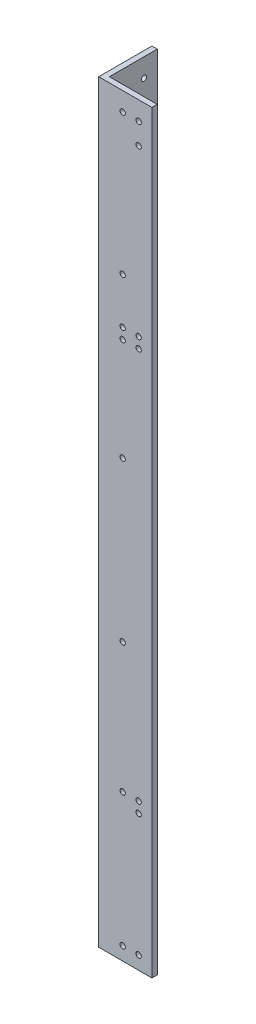
SolidWorks part; units mm, degrees
ref_plane "Front Plane" through (0, 0, 0) normal (0, 0, 1) x (1, 0, 0)
ref_plane "Top Plane" through (0, 0, 0) normal (0, 1, 0) x (1, 0, 0)
ref_plane "Right Plane" through (0, 0, 0) normal (1, 0, 0) x (0, 0, -1)
sketch "Sketch2" plane through (0, 0, 0) normal (0, 1, 0) x (1, 0, 0)
  line L0 (0, 31.75) -> (3.175, 31.75)
  line L1 (3.175, 31.75) -> (3.175, 3.175)
  line L2 (3.175, 3.175) -> (31.75, 3.175)
  line L3 (31.75, 3.175) -> (31.75, 0)
  line L4 (31.75, 0) -> (0, 0)
  line L5 (0, 0) -> (0, 31.75)
  point P9 (1.5875, 31.75)
  point P10 (31.75, 1.5875)
  dimension "D4" = 3.175
  dimension "D1" = 31.75
  dimension "D2" = 31.75
  dimension "D3" = 3.175
extrude "Boss-Extrude1" add sketch "Sketch2" along normal blind 450
sketch "BackSideHoles-Sketch3" plane through (0, 0, 0) normal (0, 0, 1) x (1, 0, 0)
  line L0 (0, 0) -> (31.75, 0) construction
  line L1 (0, 450) -> (0, 0) construction
  circle A1 centre (23.8125, 81.1125) radius 1.5875
  circle A2 centre (14.2875, 87.4625) radius 1.5875
  circle A3 centre (23.8125, 87.4625) radius 1.5875
  circle A4 centre (14.2875, 438.8875) radius 1.5875
  circle A6 centre (23.8125, 438.8875) radius 1.5875
  circle A7 centre (23.8125, 426.1875) radius 1.5875
  circle A10 centre (14.2875, 327.6026) radius 1.5875
  circle A11 centre (23.8125, 327.6026) radius 1.5875
  circle A12 centre (14.2875, 321.2526) radius 1.5875
  circle A13 centre (23.8125, 321.2526) radius 1.5875
  circle A14 centre (14.2875, 165) radius 1.5875
  circle A15 centre (14.2875, 260) radius 1.5875
  circle A16 centre (14.2875, 355) radius 1.5875
  circle A17 centre (14.2875, 7.9375) radius 1.5875
  circle A18 centre (23.8125, 7.9375) radius 1.5875
  dimension "D4" = 3.175
  dimension "D8" = 11.1125
  dimension "D7" = 6.35
  dimension "D10" = 327.6026
  dimension "D11" = 165
  dimension "D12" = 95
  dimension "D13" = 95
  dimension "D6" = 7.9375
  dimension "D5" = 6.35
  dimension "D14" = 81.1125
  dimension "D3" = 9.525
  dimension "D2" = 14.2875
  dimension "D9" = 12.7
sketch "RightSideHoles-Sketch4" plane through (0, 0, 0) normal (-1, 0, 0) x (0, 0, 1)
  line L0 (-31.75, 450) -> (0, 450) construction
  line L1 (0, 450) -> (0, 0) construction
  line L3 (-31.75, 0) -> (0, 0) construction
  circle A0 centre (-23.8125, 81.1125) radius 1.5875
  circle A2 centre (-23.8125, 87.4625) radius 1.5875
  circle A4 centre (-23.8125, 438.8875) radius 1.5875
  circle A5 centre (-14.2875, 426.1875) radius 1.5875
  circle A6 centre (-23.8125, 426.1875) radius 1.5875
  circle A10 centre (-23.8125, 327.6026) radius 1.5875
  circle A11 centre (-14.2875, 327.6026) radius 1.5875
  circle A12 centre (-23.8125, 314.9026) radius 1.5875
  circle A13 centre (-14.2875, 314.9026) radius 1.5875
  circle A14 centre (-23.8125, 7.9375) radius 1.5875
  circle A15 centre (-14.2875, 7.9375) radius 1.5875
  circle A16 centre (-14.2875, 165) radius 1.5875
  circle A17 centre (-14.2875, 260) radius 1.5875
  circle A18 centre (-14.2875, 355) radius 1.5875
  circle A19 centre (-14.2875, 81.1125) radius 1.5875
  dimension "D4" = 3.175
  dimension "D10" = 327.6026
  dimension "D13" = 95
  dimension "D5" = 6.35
  dimension "D2" = 14.2875
  dimension "D9" = 12.7
  dimension "D6" = 11.1125
  dimension "D8" = 7.9375
  dimension "D7" = 12.7
  dimension "D12" = 165
  dimension "D14" = 95
  dimension "D3" = 81.1125
  dimension "D11" = 9.525
extrude "BackSideHoles-Cut-Extrude1" cut sketch "BackSideHoles-Sketch3" against normal blind 3.175
extrude "RightSideHoles-Cut-Extrude2" cut sketch "RightSideHoles-Sketch4" against normal blind 3.175
equation "\"RailThickness\"= .125in'Spec"
equation "\"VSWidth\"= 1.25in'Spec"
equation "\"VSHeight\"= 1.25in'Spec"
equation "\"VSLength\"= 450mm"
equation "\"HoleOffsetFromEdge\"= \"RailThickness\" * 2.5"
equation "\"HoleOffsetFromSide\"= \"RailThickness\" * 3.5"
equation "\"LegHeight\"= 70mm'Space needed for PSU/Stepper/Electronics"
equation "\"VSBottomSideRailHoleY1FromBottomOfLowerRail\"= \"V1 BottomOfLowerRail\" + \"HoleOffsetFromSide\"'Equals 70.1125"
equation "\"VSSideRailHoleX1FromSide\"= \"HoleOffsetFromSide\" + \"RailThickness\""
equation "\"FasteningHoleDiameter\"= .125in"
equation "\"VSBottomSideRailHoleY2FromY1\"= \"LowerRailHeight\" - \"HoleOffsetFromSide\" - \"HoleOffsetFromEdge\"'Equals 6.35"
equation "\"VSTopSideRailHoleY1FromEdge\"= \"HoleOffsetFromEdge\" + \"RailThickness\""
equation "\"D4@BackSideHoles-Sketch3\" = \"FasteningHoleDiameter\""
equation "\"D1@Boss-Extrude1\"=\"VSLength\""
equation "\"D4@RightSideHoles-Sketch4\"=\"FasteningHoleDiameter\""
equation "\"D8@BackSideHoles-Sketch3\" = \"VSTopSideRailHoleY1FromEdge\""
equation "\"D6@RightSideHoles-Sketch4\"=\"VSTopSideRailHoleY1FromEdge\""
equation "\"VSMidSideRailHoleY1FromV8TopOfMidSideRail\"= \"V8 ToTopOfMidSideRail\" - \"HoleOffsetFromEdge\"'Equals 308.2875"
equation "\"LowerRailHeight\"= 1.00in"
equation "\"D2@Sketch2\"=\"VSWidth\""
equation "\"D1@Sketch2\"=\"VSHeight\""
equation "\"MidBackRailHeight\"= 1.00in"
equation "\"VSMidBackRailHoleY1FromV7TopOfMidBackRail\"= \"V7 ToTopOfMidBackRail\" - \"HoleOffsetFromSide\"'Equals 308.2875"
equation "\"TopRailHeight\"= 1.25in"
equation "\"MidSideRailHeight\"= 1.25in"
equation "\"D8@RightSideHoles-Sketch4\"=\"HoleOffsetFromEdge\""
equation "\"VSMidBackRailHoleY2FromY1\"= \"MidBackRailHeight\" - \"HoleOffsetFromSide\" - \"HoleOffsetFromEdge\"'Equals 6.35"
equation "\"VSMidSideRailHoleY2FromY1\"= \"MidSideRailHeight\" - \"HoleOffsetFromSide\" - \"HoleOffsetFromEdge\"'Equals 12.7"
equation "\"D7@BackSideHoles-Sketch3\"=\"VSMidBackRailHoleY2FromY1\""
equation "\"D9@RightSideHoles-Sketch4\"=\"VSMidSideRailHoleY2FromY1\""
equation "\"VSTopSideRailHoleY2FromY1\"= \"TopRailHeight\" - \"VSTopSideRailHoleY1FromEdge\" - \"HoleOffsetFromEdge\"'Equals 12.7"
equation "\"VSSideRailHoleX2FromX1\"= \"VSWidth\" - \"VSSideRailHoleX1FromSide\" - \"HoleOffsetFromEdge\""
equation "\"D7@RightSideHoles-Sketch4\"=\"VSTopSideRailHoleY2FromY1\""
equation "\"V1 BottomOfLowerRail\"= \"LegHeight\""
equation "\"StepperShaftLength\"= 24mm'Pulley will be attached to the end"
equation "\"ZAxisLeadScrewLength\"= 200mm"
equation "\"HotEndToTopOfXAxisGB\"= 63.315144mm'Measured from the100.Should be 63.315144"
equation "\"TopOfGBToBottomOfLinearRail\"= \"LinearGBWidth\" / 2 + \"LinearRailWidth\" / 2"
equation "\"LinearGBWidth\"= 27mm'Spec"
equation "\"V5 ToBottomOfXAxisLinearRail\"= \"V4 ToTopOfBuildPlate/HotEndTip\" + \"HotEndToTopOfXAxisGB\" - \"TopOfGBToBottomOfLinearRail\""
equation "\"LinearRailWidth\"= 12mm'Spec"
equation "\"V6 ToBottomOfGantryPulley\"= \"V5 ToBottomOfXAxisLinearRail\" - \"DistanceFromGABTopToLowerPulley\""
equation "\"GABUpperHeight\"= 6mm"
equation "\"GABMidWallHeight\"= 28mm'Must equal 28 or changes alignment"
equation "\"20TGT2PulleyWidth\"= 8.7mm'The STL of the Pulley in the diagram is a bit larger"
equation "\"GABMidShortRiserHeight\"= \"GABMidWallHeight\" / 2 - \"20TGT2PulleyWidth\"'Equals 5.3"
equation "\"GABRiserBossOffset\"= 0.8mm'Aligns Pulleys"
equation "\"DistanceFromGABTopToLowerPulley\"= \"GABUpperHeight\" + \"GABMidWallHeight\" - \"GABMidShortRiserHeight\" + \"GABRiserBossOffset\" / 2"
equation "\"V7 ToTopOfMidBackRail\"= \"V6 ToBottomOfGantryPulley\" + \"StepperShaftLength\""
equation "\"D10@BackSideHoles-Sketch3\" = \"VSMidBackRailHoleY1FromV7TopOfMidBackRail\""
equation "\"D10@RightSideHoles-Sketch4\"=\"VSMidSideRailHoleY1FromV8TopOfMidSideRail\""
equation "\"BedToBuildPlateStandoffLength\"= 15mm"
equation "\"BuildPlateHeight\"= 8mm'Spec"
equation "\"V4 ToTopOfBuildPlate/HotEndTip\" = \"V2 ToBedAtTopOfZAxis\" + \"BedToBuildPlateStandoffLength\" + \"BuildPlateHeight\""
equation "\"V2 ToBedAtTopOfZAxis\" = \"V1 BottomOfLowerRail\" - \"LowerEnclosureThickness\" + \"StepperShaftLength\" + \"ZAxisLeadScrewLength\" - \"LM8UUHeight\" / 2"
equation "\"LM8UUHeight\"= 24mm'Spec"
equation "\"V8 ToTopOfMidSideRail\"= \"V7 ToTopOfMidBackRail\" - \"RailThickness\""
equation "\"VSEnclosureOffsets\"= ( \"VSLength\" - \"LegHeight\" ) / 4"
equation "\"D11@BackSideHoles-Sketch3\"=\"LegHeight\" + \"VSEnclosureOffsets\""
equation "\"D12@BackSideHoles-Sketch3\"=\"VSEnclosureOffsets\""
equation "\"D13@BackSideHoles-Sketch3\"=\"VSEnclosureOffsets\""
equation "\"D12@RightSideHoles-Sketch4\"=\"LegHeight\" + \"VSEnclosureOffsets\""
equation "\"D13@RightSideHoles-Sketch4\"=\"VSEnclosureOffsets\""
equation "\"D14@RightSideHoles-Sketch4\"=\"VSEnclosureOffsets\""
equation "\"D6@BackSideHoles-Sketch3\"=\"HoleOffsetFromEdge\""
equation "\"D5@BackSideHoles-Sketch3\"=\"VSBottomSideRailHoleY2FromY1\""
equation "\"D14@BackSideHoles-Sketch3\"=\"VSBottomSideRailHoleY1FromBottomOfLowerRail\""
equation "\"D2@BackSideHoles-Sketch3\"=\"VSSideRailHoleX1FromSide\""
equation "\"D9@BackSideHoles-Sketch3\"=\"VSTopSideRailHoleY2FromY1\""
equation "\"D3@RightSideHoles-Sketch4\"=\"VSBottomSideRailHoleY1FromBottomOfLowerRail\""
equation "\"D5@RightSideHoles-Sketch4\"=\"VSBottomSideRailHoleY2FromY1\""
equation "\"D2@RightSideHoles-Sketch4\"=\"VSSideRailHoleX1FromSide\""
equation "\"D11@RightSideHoles-Sketch4\"=\"VSSideRailHoleX2FromX1\""
equation "\"LowerEnclosureThickness\"= 5mm"
